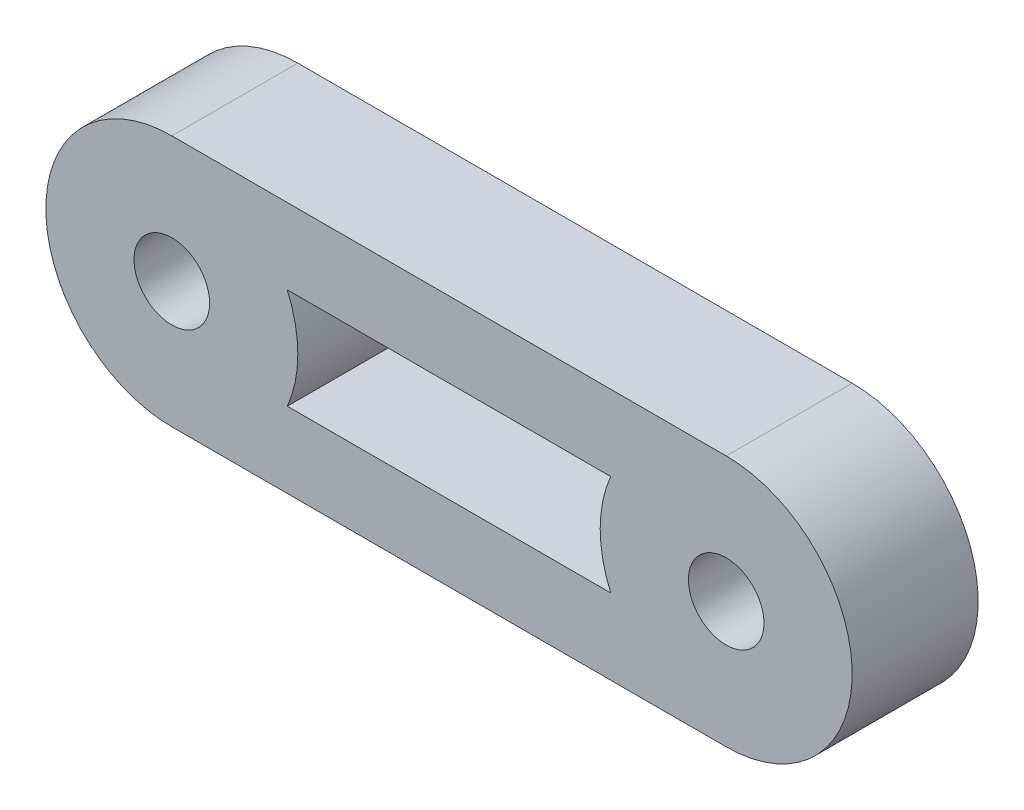
SolidWorks part; units mm, degrees
material "1060 Alloy"
ref_plane "Front Plane" through (0, 0, 0) normal (0, 0, 1) x (1, 0, 0)
ref_plane "Top Plane" through (0, 0, 0) normal (0, 1, 0) x (1, 0, 0)
ref_plane "Right Plane" through (0, 0, 0) normal (1, 0, 0) x (0, 0, -1)
sketch "Sketch1" plane through (0, 0, 0) normal (0, 0, 1) x (1, 0, 0)
  line L0 (0, 0) -> (22, 0)
  line L1 (0, -5) -> (22, -5)
  line L2 (0, 5) -> (22, 5)
  circle A0 centre (22, 0) radius 1.5
  circle A1 centre (0, 0) radius 1.5
  arc A2 (0, -5) -> (0, 5) centre (0, 0) cw
  arc A3 (22, -5) -> (22, 5) centre (22, 0) ccw
  dimension "D1" = 3
extrude "Extrude1" add sketch "Sketch1" along normal blind 5 contours L1 A3 L2 A2 A1 A0 region at (-4.6647, 0, 0)
sketch "Sketch2" plane through (0, 0, 5) normal (0, 0, 1) x (1, 0, 0)
  line L4 (0, -2) -> (22, -2)
  line L5 (22, 2) -> (0, 2)
  line L6 (4.5826, -2) -> (17.4174, -2)
  line L7 (17.4174, 2) -> (4.5826, 2)
  arc A2 (4.5826, -2) -> (4.5826, 2) centre (0, 0) ccw
  arc A3 (17.4174, 2) -> (17.4174, -2) centre (22, 0) ccw
  arc A4 (22, -2) -> (22, 2) centre (22, 0) ccw
  arc A5 (0, 2) -> (0, -2) centre (0, 0) ccw
  dimension "D1" = 3
extrude "Cut-Extrude1" cut sketch "Sketch2" against normal blind 10
move or copy body "Body-Move/Copy1" [suppressed] bodies to move or copy 103
move or copy body "Body-Move/Copy2" [suppressed] bodies to move or copy 103
